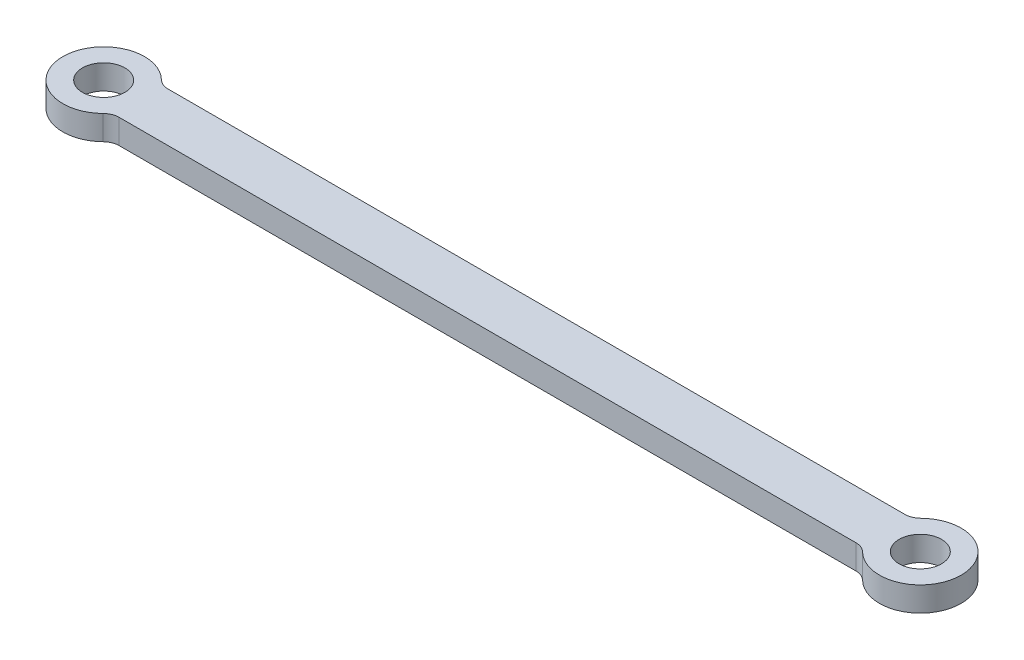
SolidWorks part; units mm, degrees
ref_plane "正面" through (0, 0, 0) normal (0, 0, 1) x (1, 0, 0)
ref_plane "平面" through (0, 0, 0) normal (0, 1, 0) x (1, 0, 0)
ref_plane "右側面" through (0, 0, 0) normal (1, 0, 0) x (0, 0, -1)
sketch "ｽｹｯﾁ1" plane through (0, 0, 0) normal (0, 1, 0) x (1, 0, 0)
  line L0 (-50, 0) -> (50, 0) construction
  line L1 (-50, 3) -> (50, 3)
  line L2 (-50, -3) -> (50, -3)
  arc A0 (-50, 3) -> (-50, -3) centre (-50, 0) ccw
  arc A1 (50, -3) -> (50, 3) centre (50, 0) ccw
  point P2 (0, 0)
  dimension "D2" = 3
  dimension "D3" = 100
extrude "ﾎﾞｽ - 押し出し1" add sketch "ｽｹｯﾁ1" along normal blind 3
sketch "ｽｹｯﾁ2" plane through (0, 3, 0) normal (0, 1, 0) x (1, 0, 0)
  circle A0 centre (-50, 0) radius 5
  circle A1 centre (50, 0) radius 5
  dimension "D1" = 10
extrude "ﾎﾞｽ - 押し出し2" add sketch "ｽｹｯﾁ2" against normal up to surface (3 mm away) up to face at (0, 0, 0)
sketch "ｽｹｯﾁ3" plane through (0, 3, 0) normal (0, 1, 0) x (1, 0, 0)
  circle A0 centre (-50, 0) radius 2.6
  circle A1 centre (50, 0) radius 2.6
  dimension "D1" = 5.2
extrude "ｶｯﾄ - 押し出し1" cut sketch "ｽｹｯﾁ3" against normal blind 10
fillet "ﾌｨﾚｯﾄ1" radius 2 4 edges at (46, 1.5, 3) (-46, 1.5, 3) (46, 1.5, -3) (-46, 1.5, -3)
